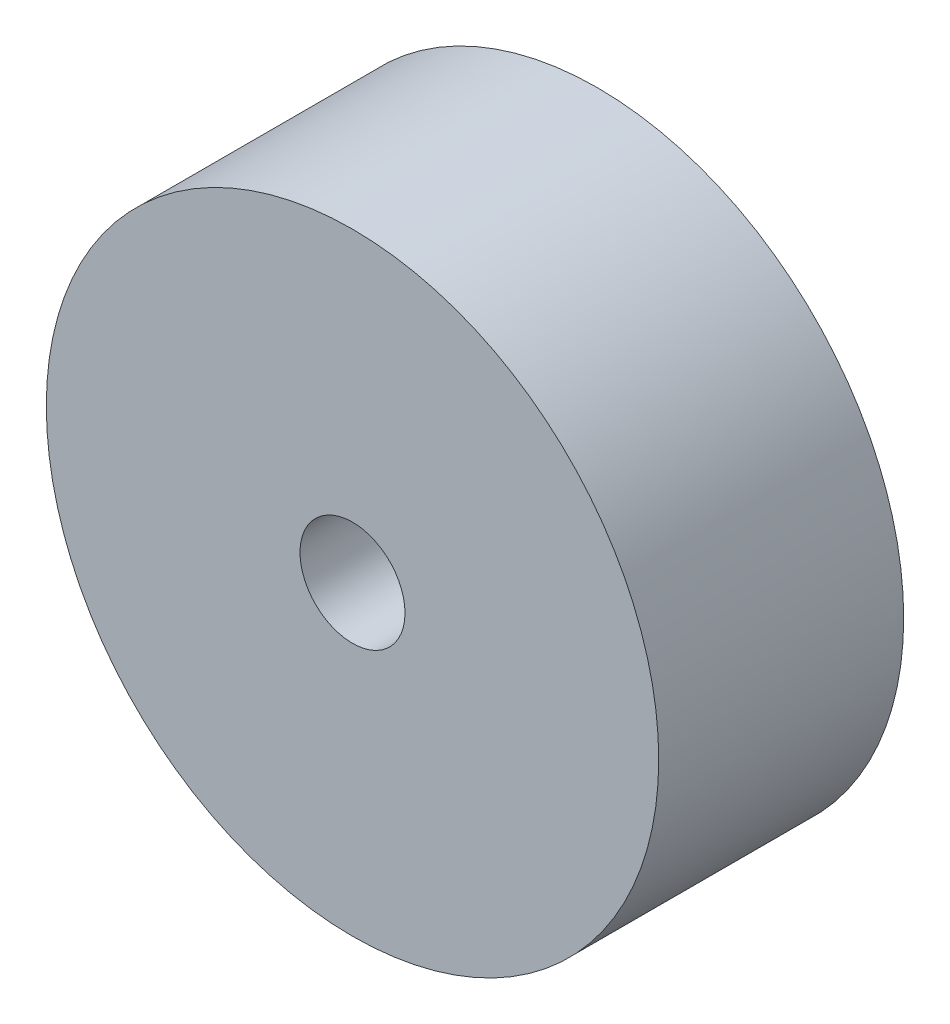
SolidWorks part; units mm, degrees
material "Beech"
ref_plane "Front Plane" through (0, 0, 0) normal (0, 0, 1) x (1, 0, 0)
ref_plane "Top Plane" through (0, 0, 0) normal (0, 1, 0) x (1, 0, 0)
ref_plane "Right Plane" through (0, 0, 0) normal (1, 0, 0) x (0, 0, -1)
sketch "Sketch1" plane through (0, 0, 0) normal (0, 0, 1) x (1, 0, 0)
  circle A0 centre (0, 0) radius 0.381
  circle A1 centre (0, 0) radius 2.2225
  dimension "D1" = 0.762
  dimension "D2" = 4.445
extrude "Boss-Extrude1" add sketch "Sketch1" along normal blind 1.778
